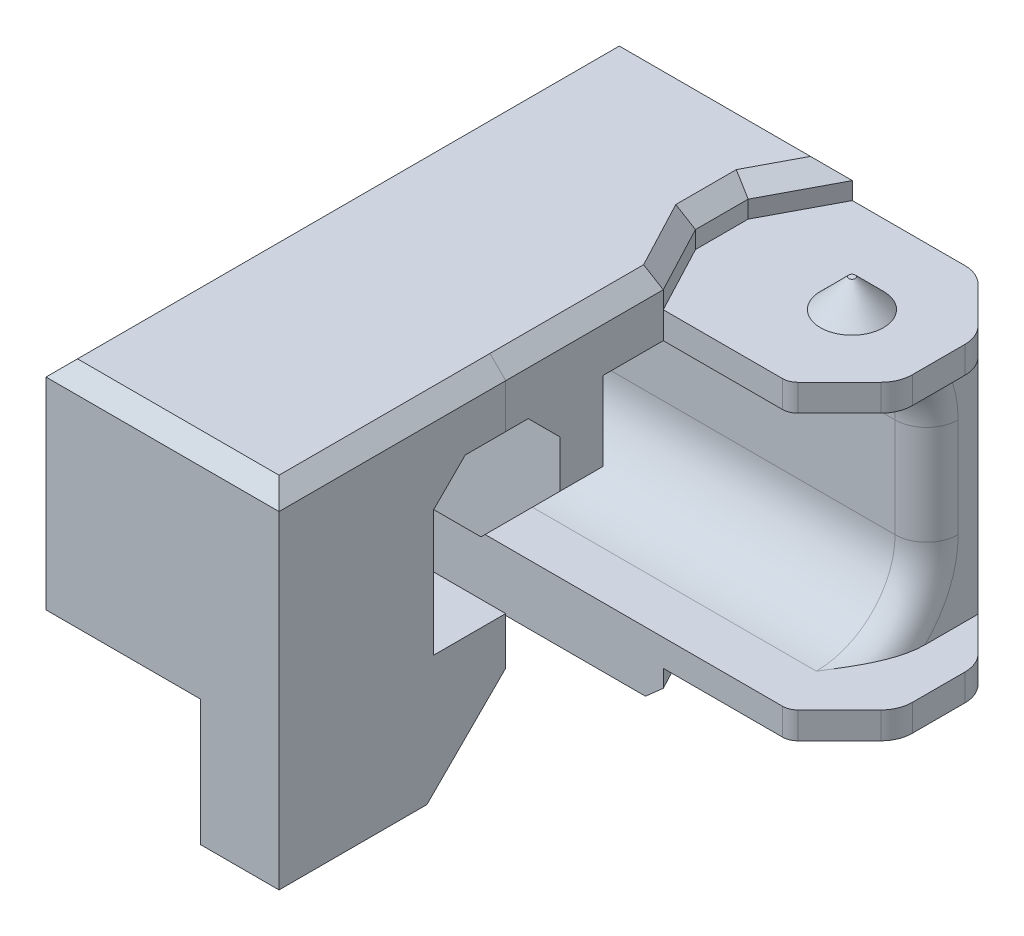
SolidWorks part; units mm, degrees
ref_plane "Plano frontal" through (0, 0, 0) normal (0, 0, 1) x (1, 0, 0)
ref_plane "Plano superior" through (0, 0, 0) normal (0, 1, 0) x (1, 0, 0)
ref_plane "Plano direito" through (0, 0, 0) normal (1, 0, 0) x (0, 0, -1)
sketch "Esboço1" plane through (0, 0, 0) normal (0, 1, 0) x (1, 0, 0)
  line L8 (4.91, 19.3882) -> (0, 19.3882)
  line L9 (0, 19.3882) -> (0, 0)
  line L10 (0, 0) -> (9.7908, 0)
  line L11 (9.7908, 0) -> (9.7908, 14.3877)
  arc A2 (9.7908, 14.3877) -> (4.91, 19.3882) centre (4.7908, 14.3896) ccw
sketch "Esboço2" plane through (0, 0, 0) normal (0, 1, 0) x (1, 0, 0)
  line L2 (14.7908, 0) -> (14.7908, 14.3867)
  line L3 (4.9594, 24.3882) -> (0, 24.3882)
  line L4 (4.91, 19.3882) -> (0, 19.3882)
  line L5 (0, 19.3882) -> (0, 0)
  line L6 (0, 0) -> (9.7908, 0)
  line L7 (9.7908, 0) -> (9.7908, 14.3877)
  line L8 (4.91, 19.3882) -> (0, 19.3882)
  line L9 (0, 24.3882) -> (0, 0)
  line L10 (0, 0) -> (14.7908, 0)
  line L11 (9.7908, 0) -> (9.7908, 14.3877)
  line L12 (-5, 24.3882) -> (-5, -5) construction
  line L13 (0, 19.3882) -> (0, 0) construction
  line L14 (4.9594, 24.3882) -> (-5, 24.3882) construction
  line L15 (-5, -5) -> (14.7908, -5) construction
  line L16 (0, 0) -> (9.7908, 0) construction
  line L17 (14.7908, -5) -> (14.7908, 14.3867) construction
  arc A0 (14.7908, 14.3867) -> (4.9594, 24.3882) centre (4.7908, 14.3896) ccw
  arc A1 (9.7908, 14.3877) -> (4.91, 19.3882) centre (4.7908, 14.3896) ccw
  arc A2 (9.7908, 14.3877) -> (4.91, 19.3882) centre (4.7908, 14.3896) ccw
  dimension "D1" = 0
  dimension "D2" = 5
extrude "Ressalto-extrusão1" add sketch "Esboço2" along normal blind 3.8 contours L11 A2 L8 L9 L10 | A2 L11 L10 L2 A0 L3 L9 L8 region at (12.2908, 0, -0.2852) region at (4.7856, 0, -9.445)
sketch "Esboço3" plane through (0, 0, 0) normal (0, 1, 0) x (1, 0, 0)
  line L0 (4.91, 19.3882) -> (0, 19.3882) construction
  line L1 (9.7908, 0) -> (9.7908, 14.3877) construction
  line L2 (4.91, 19.3882) -> (0, 19.3882)
  line L3 (9.7908, 0) -> (9.7908, 14.3877)
  line L4 (14.7908, 0) -> (14.7908, 14.3867)
  line L5 (4.9594, 24.3882) -> (0, 24.3882)
  line L6 (0, 24.3882) -> (0, 0)
  line L7 (0, 0) -> (14.7908, 0)
  line L8 (14.7908, 0) -> (14.7908, 14.3867)
  line L9 (4.9594, 24.3882) -> (0, 24.3882)
  line L10 (0, 24.3882) -> (0, 0)
  line L11 (0, 0) -> (14.7908, 0)
  line L12 (14.7908, 14.3867) -> (9.7908, 14.3877)
  arc A0 (9.7908, 14.3877) -> (4.91, 19.3882) centre (4.7908, 14.3896) ccw construction
  arc A1 (14.7908, 14.3867) -> (4.9594, 24.3882) centre (4.7908, 14.3896) ccw
  arc A2 (14.7908, 14.3867) -> (4.9594, 24.3882) centre (4.7908, 14.3896) ccw
  arc A3 (9.7908, 14.3877) -> (4.91, 19.3882) centre (4.7908, 14.3896) ccw
  dimension "D1" = 0
sketch "Esboço4" plane through (0, 3.8, 0) normal (0, 1, 0) x (1, 0, 0)
  line L0 (9.7908, 0) -> (9.7908, 14.3877) construction
  line L3 (4.91, 19.3882) -> (0, 19.3882) construction
  circle A0 centre (4.2608, 13.8182) radius 1.75
  dimension "D3" = 3.5
  dimension "D1" = 5.53
  dimension "D2" = 5.57
sketch "Esboço7" plane through (0, 3.8, 0) normal (0, 1, 0) x (1, 0, 0)
  line L33 (0, 36.3882) -> (0, 24.3882)
  line L34 (0, 24.3882) -> (22.352, 24.3882)
  line L35 (23.0591, 24.6811) -> (25.6804, 27.3024)
  line L36 (26.2662, 28.7166) -> (26.2662, 32.0597)
  line L37 (25.6804, 33.474) -> (23.352, 35.8024)
  line L38 (21.9378, 36.3882) -> (19.75, 36.3882)
  line L39 (19.75, 36.3882) -> (0, 36.3882)
  line L40 (14.7908, 14.3896) -> (14.7908, 24.3882)
  line L42 (0, 24.3882) -> (14.7908, 24.3882)
  line L43 (0, 24.3882) -> (0, 14.3896)
  line L44 (0, 14.3896) -> (14.7908, 14.3896)
  line L45 (14.7908, 24.3882) -> (14.7908, 14.3896)
  arc A18 (22.352, 24.3882) -> (23.0591, 24.6811) centre (22.352, 25.3882) ccw
  arc A19 (25.6804, 27.3024) -> (26.2662, 28.7166) centre (24.2662, 28.7166) ccw
  arc A20 (26.2662, 32.0597) -> (25.6804, 33.474) centre (24.2662, 32.0597) ccw
  arc A21 (23.352, 35.8024) -> (21.9378, 36.3882) centre (21.9378, 34.3882) ccw
  arc A22 (14.7908, 14.3867) -> (4.9594, 24.3882) centre (4.7908, 14.3896) ccw construction
  arc M2 (14.7908, 14.3867) -> (4.9594, 24.3882) centre (4.7908, 14.3896) ccw
  line M4 (4.9594, 24.3882) -> (0, 24.3882)
extrude "Corte-extrusão1" cut sketch "Esboço4" against normal blind 10
extrude "Ressalto-extrusão2" add sketch "Esboço3" against normal blind 18 contours L8 L12 L3 L11 region at (12.2908, 0, -7.1936)
extrude "Ressalto-extrusão3" add sketch "Esboço7" against normal up to surface (3.8 mm away) contours L37 A21 L38 L39 L33 L34 A18 L35 A19 L36 A20 M4 | L40 L34 M2 region at (12.638, 3.8, -30.3869) region at (12.5589, 3.8, -22.1545) up to face at (4.2608, 0, -12.0682)
sketch "Esboço8" plane through (0, 3.8, 0) normal (0, 1, 0) x (1, 0, 0)
  line L0 (14.7908, 24.3882) -> (12.5051, 28.7166)
  line L1 (12.5051, 28.7166) -> (12.5051, 32.0597)
  line L2 (12.5051, 32.0597) -> (14.7908, 36.3882)
  line L10 (0, 0) -> (14.7908, 0)
  line L11 (14.7908, 0) -> (14.7908, 14.3867)
  line L12 (14.7908, 14.3867) -> (14.7908, 14.3896)
  line L13 (14.7908, 14.3896) -> (14.7908, 24.3882)
  line L14 (14.7908, 24.3882) -> (22.352, 24.3882)
  line L15 (23.0591, 24.6811) -> (25.6804, 27.3024)
  line L16 (26.2662, 28.7166) -> (26.2662, 32.0597)
  line L17 (25.6804, 33.474) -> (23.352, 35.8024)
  line L18 (21.9378, 36.3882) -> (0, 36.3882)
  line L19 (0, 36.3882) -> (0, 0)
  line L22 (14.7908, 14.3867) -> (14.7908, 14.3896)
  line L24 (14.7908, 24.3882) -> (22.352, 24.3882)
  line L25 (23.0591, 24.6811) -> (25.6804, 27.3024)
  line L26 (26.2662, 28.7166) -> (26.2662, 32.0597)
  line L27 (25.6804, 33.474) -> (23.352, 35.8024)
  line L28 (21.9378, 36.3882) -> (14.7908, 36.3882)
  arc A4 (22.352, 24.3882) -> (23.0591, 24.6811) centre (22.352, 25.3882) ccw
  arc A5 (25.6804, 27.3024) -> (26.2662, 28.7166) centre (24.2662, 28.7166) ccw
  arc A6 (26.2662, 32.0597) -> (25.6804, 33.474) centre (24.2662, 32.0597) ccw
  arc A7 (23.352, 35.8024) -> (21.9378, 36.3882) centre (21.9378, 34.3882) ccw
  arc A8 (22.352, 24.3882) -> (23.0591, 24.6811) centre (22.352, 25.3882) ccw
  arc A9 (25.6804, 27.3024) -> (26.2662, 28.7166) centre (24.2662, 28.7166) ccw
  arc A10 (26.2662, 32.0597) -> (25.6804, 33.474) centre (24.2662, 32.0597) ccw
  arc A11 (23.352, 35.8024) -> (21.9378, 36.3882) centre (21.9378, 34.3882) ccw
  line M20 (14.7908, 24.3882) -> (22.352, 24.3882)
  arc M21 (22.352, 24.3882) -> (23.0591, 24.6811) centre (22.352, 25.3882) ccw
  line M22 (23.0591, 24.6811) -> (25.6804, 27.3024)
  arc M23 (25.6804, 27.3024) -> (26.2662, 28.7166) centre (24.2662, 28.7166) ccw
  line M24 (26.2662, 28.7166) -> (26.2662, 32.0597)
  arc M25 (26.2662, 32.0597) -> (25.6804, 33.474) centre (24.2662, 32.0597) ccw
  line M26 (25.6804, 33.474) -> (23.352, 35.8024)
  arc M27 (23.352, 35.8024) -> (21.9378, 36.3882) centre (21.9378, 34.3882) ccw
  line M28 (21.9378, 36.3882) -> (0, 36.3882)
  dimension "D1" = 0
extrude "Corte-extrusão2" cut sketch "Esboço8" against normal blind 2.1 contours L2 L1 L0 M20 M21 M22 M23 M24 M25 M26 M27 M28 region at (19.3087, 3.8, -30.3855)
ref_plane "Plano1" through (0, -16.31, 0) normal (0, -1, 0) x (-1, 0, 0)
sketch "Esboço9" plane through (0, -16.31, 0) normal (0, -1, 0) x (-1, 0, 0)
  line L0 (-14.7908, 24.3882) -> (0, 24.3882)
  line L11 (-14.7908, 24.3882) -> (-14.7908, 14.3896)
  line L12 (-14.7908, 14.3896) -> (-14.7908, 14.3867)
  line L13 (-14.7908, 14.3867) -> (-9.7908, 14.3877)
  line L14 (-9.7908, 14.3877) -> (-9.7908, 0)
  line L15 (-9.7908, 0) -> (0, 0)
  line L16 (0, 0) -> (0, 36.3882)
  line L17 (0, 36.3882) -> (-21.9378, 36.3882)
  line L18 (-23.352, 35.8024) -> (-25.6804, 33.474)
  line L19 (-26.2662, 32.0597) -> (-26.2662, 28.7166)
  line L20 (-25.6804, 27.3024) -> (-23.0591, 24.6811)
  line L21 (-22.352, 24.3882) -> (-14.7908, 24.3882)
  line L23 (-14.7908, 14.3896) -> (-14.7908, 14.3867)
  line L27 (0, 24.3882) -> (0, 36.3882)
  line L28 (0, 36.3882) -> (-21.9378, 36.3882)
  line L29 (-23.352, 35.8024) -> (-25.6804, 33.474)
  line L30 (-26.2662, 32.0597) -> (-26.2662, 28.7166)
  line L31 (-25.6804, 27.3024) -> (-23.0591, 24.6811)
  line L32 (-22.352, 24.3882) -> (-14.7908, 24.3882)
  arc A4 (-21.9378, 36.3882) -> (-23.352, 35.8024) centre (-21.9378, 34.3882) ccw
  arc A5 (-25.6804, 33.474) -> (-26.2662, 32.0597) centre (-24.2662, 32.0597) ccw
  arc A6 (-26.2662, 28.7166) -> (-25.6804, 27.3024) centre (-24.2662, 28.7166) ccw
  arc A7 (-23.0591, 24.6811) -> (-22.352, 24.3882) centre (-22.352, 25.3882) ccw
  arc A8 (-21.9378, 36.3882) -> (-23.352, 35.8024) centre (-21.9378, 34.3882) ccw
  arc A9 (-25.6804, 33.474) -> (-26.2662, 32.0597) centre (-24.2662, 32.0597) ccw
  arc A10 (-26.2662, 28.7166) -> (-25.6804, 27.3024) centre (-24.2662, 28.7166) ccw
  arc A11 (-23.0591, 24.6811) -> (-22.352, 24.3882) centre (-22.352, 25.3882) ccw
  dimension "D1" = 0
extrude "Ressalto-extrusão4" add sketch "Esboço9" along normal blind 1.7 separate body contours L31 A11 L32 L0 L27 L28 A8 L29 A9 L30 A10 region at (12.638, -16.31, -30.3869)
sketch "Esboço11" plane through (0, -18.01, 0) normal (0, -1, 0) x (1, 0, 0)
  line L0 (14.7908, -24.3882) -> (0, -24.3882)
  line L9 (12.5051, -32.0597) -> (12.5051, -28.7166)
  line L10 (14.7908, -36.3882) -> (12.5051, -32.0597)
  line L11 (0, -36.3882) -> (14.7908, -36.3882)
  line L12 (0, 0) -> (0, -36.3882)
  line L13 (14.7908, 0) -> (0, 0)
  line L14 (14.7908, -14.3867) -> (14.7908, 0)
  line L15 (14.7908, -14.3896) -> (14.7908, -14.3867)
  line L16 (14.7908, -24.3882) -> (14.7908, -14.3896)
  line L17 (12.5051, -28.7166) -> (14.7908, -24.3882)
  line L18 (12.5051, -32.0597) -> (12.5051, -28.7166)
  line L19 (14.7908, -36.3882) -> (12.5051, -32.0597)
  line L20 (0, -36.3882) -> (14.7908, -36.3882)
  line L21 (0, -24.3882) -> (0, -36.3882)
  line L24 (14.7908, -14.3896) -> (14.7908, -14.3867)
  line L26 (12.5051, -28.7166) -> (14.7908, -24.3882)
  line M12 (22.352, -24.3882) -> (0, -24.3882)
  line M13 (0, -24.3882) -> (0, -36.3882)
  line M14 (0, -36.3882) -> (21.9378, -36.3882)
  dimension "D1" = 0
extrude "Ressalto-extrusão5" add sketch "Esboço11" along normal blind 2.1 contours L18 L26 L19 M12 M13 M14 region at (6.6864, -18.01, -30.3882)
sketch "Esboço12" plane through (0, 0, -36.3882) normal (0, 0, -1) x (-1, 0, 0)
  line L0 (-12.5051, 3.8) -> (-12.5051, -20.11)
  line L1 (-12.5051, 3.8) -> (0, 3.8)
  line L3 (-12.5051, -20.11) -> (0, -20.11)
  line L4 (0, 3.8) -> (0, -20.11)
extrude "Ressalto-extrusão6" add sketch "Esboço12" against normal blind 4
sketch "Esboço13" plane through (0, 1.7, 0) normal (0, 1, 0) x (1, 0, 0)
  line L0 (26.2662, 30.3882) -> (20.7662, 30.3882) construction
  line L1 (26.2662, 28.7166) -> (26.2662, 32.0597) construction
  circle A0 centre (20.7662, 30.3882) radius 2
  dimension "D2" = 4
  dimension "D1" = 5.5
extrude "Ressalto-extrusão7" add sketch "Esboço13" along normal blind 1.8 draft 45
ref_plane "Plano2" through (0, -8.155, 0) normal (0, 1, 0) x (1, 0, 0)
mirror "Espelhar1" about plane through (0, -8.155, 0) normal (0, 1, 0) of "Ressalto-extrusão7"
fillet "Filete2" radius 5 2 edges at (6.2525, -16.31, -32.3882) (6.2525, 0, -32.3882)
chamfer "Chanfro1" distance 1 angle 45 2 edges at (7.3954, -20.11, -36.3882) (7.3954, 3.8, -36.3882)
chamfer "Chanfro2" distance 5 angle 45 1 edges at (12.2908, -18, -14.3872)
chamfer "Chanfro3" distance 1 angle 45 6 edges at (13.3839, 3.8, -33.724) (12.5051, 3.8, -30.3882) (13.648, 3.8, -26.5524) (14.7908, 3.8, -19.3889) (14.7908, 3.8, -14.3882) (14.7908, 3.8, -7.1934)
chamfer "Chanfro4" distance 1 angle 45 2 edges at (6.8954, 3.8, 0) (0, 3.8, -17.6941)
chamfer "Chanfro5" distance 1 angle 45 3 edges at (13.3839, -20.11, -33.724) (12.5051, -20.11, -30.3882) (13.648, -20.11, -26.5524)
sketch "Esboço15" plane through (0, 0, 0) normal (0, -1, 0) x (1, 0, 0)
  line L0 (9.7908, 0) -> (9.7908, -9.3877) construction
  line L1 (9.7908, -14.3877) -> (9.7908, -9.3877) construction
  line L2 (0, -27.3882) -> (0, 0) construction
  line L3 (0, 0) -> (9.7908, 0) construction
  line L4 (9.7908, 0) -> (9.7908, -9.3877)
  line L5 (9.7908, -14.3877) -> (9.7908, -9.3877)
  line L6 (0, -20.5683) -> (0, 0)
  line L7 (0, 0) -> (9.7908, 0)
  line L8 (9.7908, -14.3877) -> (0, -20.5683)
  circle A0 centre (4.2608, -13.8182) radius 1.75 construction
  circle A1 centre (4.2608, -13.8182) radius 1.75
extrude "Ressalto-extrusão8" add sketch "Esboço15" along normal blind 10
sketch "Esboço14" plane through (0, 3.8, 0) normal (0, 1, 0) x (1, 0, 0)
  circle A0 centre (4.2608, 13.8182) radius 3
  dimension "D1" = 6
extrude "Corte-extrusão3" cut sketch "Esboço14" against normal blind 12.5
sketch "Esboço16" plane through (12.5051, 0, 0) normal (1, 0, 0) x (0, 0, -1)
  line L4 (36.3882, 0) -> (27.3882, 0)
  line L5 (32.3882, -5) -> (32.3882, -11.31)
  line L6 (27.3882, -16.31) -> (36.3882, -16.31)
  line L7 (36.3882, -16.31) -> (36.3882, 0)
  line L8 (36.3882, 0) -> (27.3882, 0)
  line L9 (32.3882, -5) -> (32.3882, -11.31)
  line L10 (27.3882, -16.31) -> (36.3882, -16.31)
  line L11 (36.3882, -16.31) -> (36.3882, 0)
  arc A2 (32.3882, -5) -> (27.3882, 0) centre (27.3882, -5) ccw
  arc A3 (27.3882, -16.31) -> (32.3882, -11.31) centre (27.3882, -11.31) ccw
  arc A4 (32.3882, -5) -> (27.3882, 0) centre (27.3882, -5) ccw
  arc A5 (27.3882, -16.31) -> (32.3882, -11.31) centre (27.3882, -11.31) ccw
  dimension "D1" = 0
extrude "Ressalto-extrusão9" add sketch "Esboço16" along normal blind 11
sketch "Esboço19" plane through (0, -16.31, 0) normal (0, -1, 0) x (1, 0, 0)
  line L3 (23.5051, -35.6493) -> (23.352, -35.8024)
  line L4 (21.9378, -36.3882) -> (23.5051, -36.3882)
  line L5 (23.5051, -36.3882) -> (23.5051, -35.6493)
  line L6 (23.5051, -35.6493) -> (23.352, -35.8024)
  line L7 (21.9378, -36.3882) -> (23.5051, -36.3882)
  line L8 (23.5051, -36.3882) -> (23.5051, -35.6493)
  arc A1 (21.9378, -36.3882) -> (23.352, -35.8024) centre (21.9378, -34.3882) ccw
  arc A2 (21.9378, -36.3882) -> (23.352, -35.8024) centre (21.9378, -34.3882) ccw
  dimension "D1" = 0
extrude "Corte-extrusão5" cut sketch "Esboço19" against normal blind 21
fillet "Filete4" radius 2 3 edges at (23.5051, -1.4645, -30.9237) (23.5051, -14.8455, -30.9237) (23.5051, -8.155, -32.3882)
sketch "Esboço20" plane through (14.7908, 0, 0) normal (1, 0, 0) x (0, 0, -1)
  line L0 (14.3867, 2.8) -> (0, 2.8) construction
  line L1 (20.5683, -10) -> (13.6684, -10)
  line L2 (20.5683, -10) -> (20.5683, 2.8)
  line L3 (20.5683, 2.8) -> (13.6684, 2.8)
  line L4 (13.6684, -10) -> (13.6684, 2.8)
  line L5 (20.5683, -10) -> (13.6684, 2.8) construction
  line L6 (20.5683, 2.8) -> (13.6684, -10) construction
  point P4 (17.1184, -3.6)
  point P6 (13.6684, 2.8)
  point P7 (0, 0)
extrude "Ressalto-extrusão10" add sketch "Esboço20" against normal up to surface (3.8606 mm away) up to face at (4.8954, -5, -17.478)
sketch "Esboço25" plane through (0, 3.8, 0) normal (0, 1, 0) x (1, 0, 0)
  circle A0 centre (4.2608, 13.8182) radius 1.75 construction
  circle A1 centre (4.2608, 13.8182) radius 3
  circle A2 centre (4.2608, 13.8182) radius 3 construction
  circle A3 centre (4.2608, 13.8182) radius 1.75 construction
  dimension "D1" = 0
sketch "Esboço26" plane through (0, -10, 0) normal (0, -1, 0) x (1, 0, 0)
  line L0 (14.7908, -14.3867) -> (14.7908, -20.5683) construction
  line L1 (14.7908, -17.8182) -> (1, -17.8182)
  line L2 (14.7908, -17.8182) -> (14.7908, -9.8182)
  line L3 (14.7908, -9.8182) -> (1, -9.8182)
  line L4 (1, -17.8182) -> (1, -9.8182)
  line L5 (14.7908, -17.8182) -> (1, -9.8182) construction
  line L6 (14.7908, -9.8182) -> (1, -17.8182) construction
  line L7 (4.2608, -13.8182) -> (14.7908, -13.8182) construction
  line L8 (1, -35.3882) -> (1, -1) construction
  point P4 (7.8954, -13.8182)
  point P10 (8.3249, -13.8182)
  dimension "D1" = 8
extrude "Corte-extrusão10" cut sketch "Esboço26" against normal blind 10
sketch "Esboço27" plane through (1, 0, 0) normal (1, 0, 0) x (0, 0, -1)
  line L0 (13.8182, 3.8) -> (13.8182, -10) construction
  line L1 (16.8182, 3.8) -> (10.8182, 3.8) construction
  line L2 (14.3867, -10) -> (9.8182, -10) construction
  line L3 (13.8182, -10) -> (13.8182, -6.1573) construction
  line L4 (11.7182, -10) -> (11.7182, -6.1573)
  line L5 (15.9182, -10) -> (15.9182, -6.1573)
  arc A0 (11.7182, -10) -> (15.9182, -10) centre (13.8182, -10) ccw
  arc A1 (15.9182, -6.1573) -> (11.7182, -6.1573) centre (13.8182, -6.1573) ccw
  point P6 (13.8182, -8.0786)
  point P12 (13.8182, -6.1573)
  dimension "D1" = 4.2
extrude "Corte-extrusão11" cut sketch "Esboço27" against normal blind 10
chamfer "Chanfro10" distance 1 angle 45 2 edges at (0.5, -10, -15.9182) (0.5, -10, -11.7182)
sketch "Esboço28" plane through (0, 3.8, 0) normal (0, 1, 0) x (1, 0, 0)
  circle A0 centre (4.2608, 13.8182) radius 3.1624
extrude "Ressalto-extrusão11" add sketch "Esboço28" against normal up to surface (3.8 mm away) up to face at (10.1939, 0, -14.0082)
chamfer "Chanfro11" distance 5 angle 45 1 edges at (14.7908, -10, -19.1933)
chamfer "Chanfro12" distance 2 angle 45 3 edges at (7.8954, 0, -17.8182) (1, 0, -13.8182) (7.8954, 0, -9.8182)
